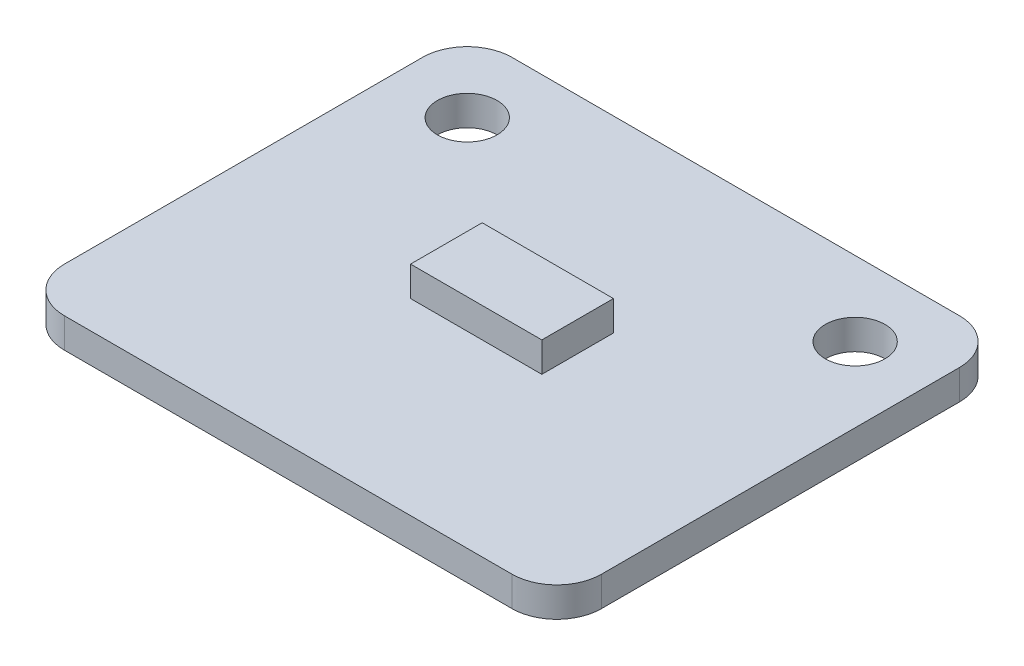
SolidWorks part; units mm, degrees
ref_plane "Front Plane" through (0, 0, 0) normal (0, 0, 1) x (1, 0, 0)
ref_plane "Top Plane" through (0, 0, 0) normal (0, 1, 0) x (1, 0, 0)
ref_plane "Right Plane" through (0, 0, 0) normal (1, 0, 0) x (0, 0, -1)
sketch "Sketch1" plane through (0, 0, 0) normal (0, 1, 0) x (1, 0, 0)
  line L0 (-6.5, 5) -> (0, 0) construction
  line L1 (-9, -7.5) -> (9, -7.5)
  line L2 (-9, -7.5) -> (-9, 7.5)
  line L3 (-9, 7.5) -> (9, 7.5)
  line L4 (9, -7.5) -> (9, 7.5)
  line L5 (-9, -7.5) -> (9, 7.5) construction
  line L6 (-9, 7.5) -> (9, -7.5) construction
  line L7 (0, 0) -> (6.5, 5) construction
  line L9 (-2.2, 1.2) -> (2.2, 1.2)
  line L10 (-2.2, 1.2) -> (-2.2, -1.2)
  line L11 (-2.2, -1.2) -> (2.2, -1.2)
  line L12 (2.2, 1.2) -> (2.2, -1.2)
  line L13 (-2.2, 1.2) -> (2.2, -1.2) construction
  line L14 (-2.2, -1.2) -> (2.2, 1.2) construction
  circle A0 centre (-6.5, 5) radius 1
  circle A1 centre (6.5, 5) radius 1
  point P0 (0, 0)
  point P15 (0, 0)
  point P16 (0, 0)
  point P17 (0, 0)
  point P18 (0, 0)
  dimension "D3" = 2
  dimension "D1" = 18
  dimension "D2" = 15
  dimension "D4" = 13
  dimension "D5" = 2.5
  dimension "D6" = 2.4
  dimension "D7" = 4.4
extrude "Boss-Extrude1" add sketch "Sketch1" against normal blind 1 contours L1 L4 L3 L2 | A0 | A1
extrude "Boss-Extrude2" add sketch "Sketch1<4>" along normal blind 1 contours L11 L12 L9 L10
sketch "Sketch1<4>" plane through (0, 0, 0) normal (0, 1, 0) x (1, 0, 0) same geometry as "Sketch1"
fillet "Fillet1" radius 1.5 4 edges at (-9, -0.5, -7.5) (9, -0.5, -7.5) (9, -0.5, 7.5) (-9, -0.5, 7.5)
